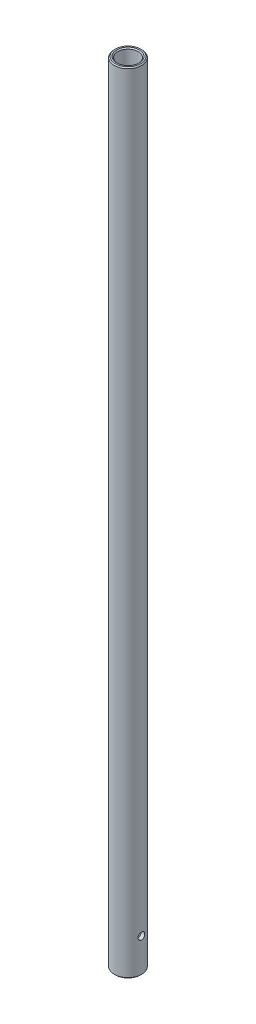
SolidWorks part; units mm, degrees
material "AISI 304"
ref_plane "Спереди" through (0, 0, 0) normal (0, 0, 1) x (1, 0, 0)
ref_plane "Сверху" through (0, 0, 0) normal (0, 1, 0) x (1, 0, 0)
ref_plane "Справа" through (0, 0, 0) normal (1, 0, 0) x (0, 0, -1)
other "Configuration Table"
sketch "Эскиз1" plane through (0, 0, 0) normal (0, 1, 0) x (1, 0, 0)
  circle A0 centre (0, 0) radius 4
  circle A1 centre (0, 0) radius 3
  dimension "D1" = 8
  dimension "D2" = 6
extrude "Бобышка-Вытянуть1" add sketch "Эскиз1" along normal blind 230
chamfer "Фаска1" distance 0.3 angle 45 4 edges at (0, 230, 3) (0, 0, 3) (0, 0, 4) (0, 230, 4)
sketch "Эскиз2" plane through (0, 0, 0) normal (1, 0, 0) x (0, 0, -1)
  circle A0 centre (0, 10) radius 1 construction
  circle A1 centre (0, 10) radius 1
extrude "Вырез-Вытянуть1" cut sketch "Эскиз2" against normal through all both and the other way through all
